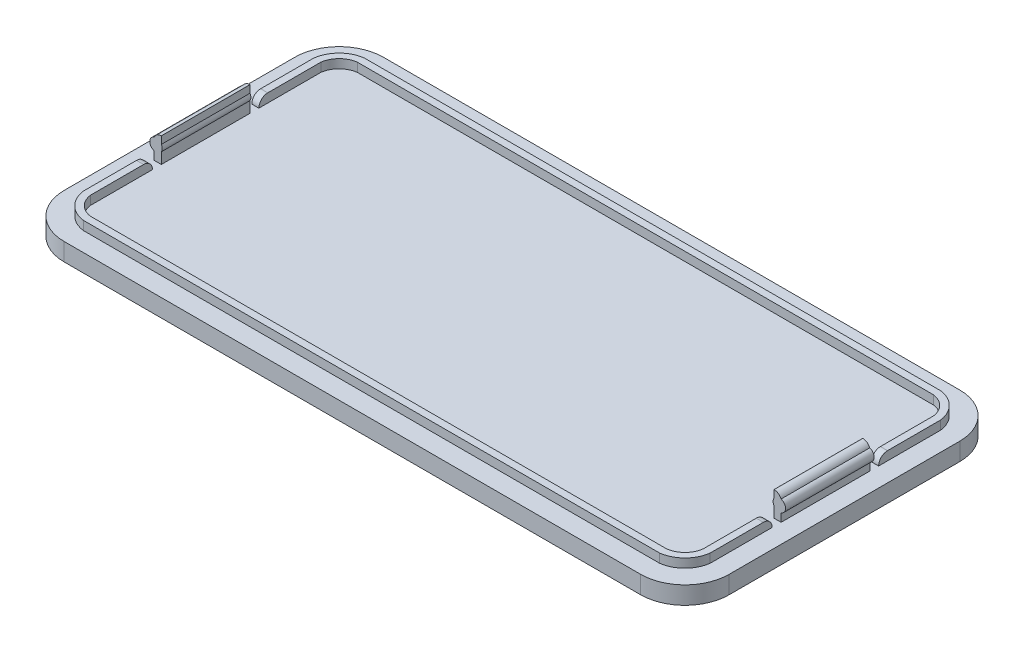
SolidWorks part; units mm, degrees
ref_plane "前视基准面" through (0, 0, 0) normal (0, 0, 1) x (1, 0, 0)
ref_plane "上视基准面" through (0, 0, 0) normal (0, 1, 0) x (1, 0, 0)
ref_plane "右视基准面" through (0, 0, 0) normal (1, 0, 0) x (0, 0, -1)
sketch "zero" plane through (0, 0, 0) normal (0, 1, 0) x (1, 0, 0)
  line L1 (-29.5, 15) -> (29.5, 15)
  line L2 (-32.5, 12) -> (-32.5, -12)
  line L3 (-29.5, -15) -> (29.5, -15)
  line L4 (32.5, 12) -> (32.5, -12)
  line L5 (-32.5, 15) -> (32.5, -15) construction
  line L6 (-32.5, -15) -> (32.5, 15) construction
  line L7 (-25.7, -15) -> (-14.5, -15)
  line L8 (-25.7, -15) -> (-25.7, -9.6569)
  line L9 (-25.7, -9.6569) -> (-14.5, -9.6569)
  line L10 (-14.5, -15) -> (-14.5, -9.6569)
  line L11 (5.2, -15) -> (12.7, -15)
  line L12 (5.2, -15) -> (5.2, -11)
  line L13 (5.2, -11) -> (12.7, -11)
  line L14 (12.7, -15) -> (12.7, -11)
  line L15 (17.8, -15) -> (25.3, -15)
  line L16 (17.8, -15) -> (17.8, -11)
  line L17 (17.8, -11) -> (25.3, -11)
  line L18 (25.3, -15) -> (25.3, -11)
  line L19 (-32.5, 7.7) -> (-19.5, 7.7)
  line L20 (-32.5, 7.7) -> (-32.5, -4.3)
  line L21 (-32.5, -4.3) -> (-19.5, -4.3)
  line L22 (-19.5, 7.7) -> (-19.5, -4.3)
  line L23 (-25.5, 14) -> (25.5, 14)
  line L24 (-25.5, 14) -> (-25.5, 8.8)
  line L25 (-25.5, 8.8) -> (25.5, 8.8)
  line L26 (25.5, 14) -> (25.5, 8.8)
  line L27 (-19.5, 7.2329) -> (-35.5, 7.2329)
  line L28 (-19.5, 7.2329) -> (-19.5, -3.7671)
  line L29 (-19.5, -3.7671) -> (-35.5, -3.7671)
  line L30 (-35.5, 7.2329) -> (-35.5, -3.7671)
  arc A0 (29.5, -15) -> (32.5, -12) centre (29.5, -12) ccw
  arc A1 (29.5, 15) -> (32.5, 12) centre (29.5, 12) cw
  arc A2 (-32.5, -12) -> (-29.5, -15) centre (-29.5, -12) ccw
  arc A3 (-29.5, 15) -> (-32.5, 12) centre (-29.5, 12) ccw
  circle A4 centre (-29, 11.4) radius 3
  circle A5 centre (-29, -11.5) radius 3
  circle A6 centre (29, 11.4) radius 3
  circle A7 centre (29, -11.5) radius 3
  circle A8 centre (-29, 11.4) radius 1.375
  circle A9 centre (-29, -11.5) radius 1.375
  circle A10 centre (29, -11.5) radius 1.375
  circle A11 centre (29, 11.4) radius 1.375
  point P0 (0, 0)
  dimension "D3" = 3
  dimension "D4" = 6
  dimension "D9" = 2.75
  dimension "D1" = 65
  dimension "D2" = 30
  dimension "D5" = 3.6
  dimension "D6" = 3.5
  dimension "D7" = 3.5
  dimension "D8" = 3.5
  dimension "D10" = 12
  dimension "D11" = 7.3
  dimension "D12" = 13
  dimension "D13" = 11.2
  dimension "D14" = 6.8
  dimension "D15" = 19.7
  dimension "D16" = 7.5
  dimension "D17" = 7.5
  dimension "D18" = 5.1
  dimension "D19" = 4
  dimension "D20" = 5.2
  dimension "D21" = 7
  dimension "D22" = 7
  dimension "D23" = 1
  dimension "D24" = 11
  dimension "D25" = 16
sketch "sugar" plane through (0, 0, 0) normal (0, 1, 0) x (1, 0, 0)
  line L1 (-29.5, 15) -> (29.5, 15)
  line L2 (-32.5, 12) -> (-32.5, -12)
  line L3 (-29.5, -15) -> (29.5, -15)
  line L4 (32.5, 12) -> (32.5, -12)
  line L5 (-32.5, 15) -> (32.5, -15) construction
  line L6 (-32.5, -15) -> (32.5, 15) construction
  line L7 (23.5, -11.5) -> (19.5, -11.5)
  line L8 (23.5, -11.5) -> (23.5, -13.9082)
  line L9 (23.5, -13.9082) -> (19.5, -13.9082)
  line L10 (19.5, -11.5) -> (19.5, -13.9082)
  line L11 (16, -11.0071) -> (8.5, -11.0071)
  line L12 (16, -11.0071) -> (16, -15)
  line L13 (16, -15) -> (8.5, -15)
  line L14 (8.5, -11.0071) -> (8.5, -15)
  line L15 (20.5, -13.9082) -> (22.5, -13.9082)
  line L16 (20.5, -13.9082) -> (20.5, -14.8173)
  line L17 (20.5, -14.8173) -> (22.5, -14.8173)
  line L18 (22.5, -13.9082) -> (22.5, -14.8173)
  arc A0 (29.5, 15) -> (32.5, 12) centre (29.5, 12) cw
  arc A1 (29.5, -15) -> (32.5, -12) centre (29.5, -12) ccw
  arc A2 (-32.5, -12) -> (-29.5, -15) centre (-29.5, -12) ccw
  arc A3 (-29.5, 15) -> (-32.5, 12) centre (-29.5, 12) ccw
  circle A4 centre (-29, 11.4) radius 3
  circle A5 centre (-29, 11.4) radius 1.375
  circle A6 centre (-29, -11.5) radius 3
  circle A7 centre (-29, -11.5) radius 1.375
  circle A8 centre (29, 11.4) radius 3
  circle A9 centre (29, 11.4) radius 1.375
  circle A10 centre (29, -11.5) radius 3
  circle A11 centre (29, -11.5) radius 1.375
  dimension "D3" = 3
  dimension "D1" = 65
  dimension "D2" = 30
  dimension "D4" = 9
  dimension "D5" = 4
  dimension "D6" = 3.5
  dimension "D7" = 7.5
  dimension "D8" = 2
  dimension "D9" = 1
sketch "case" plane through (0, 0, 0) normal (0, 1, 0) x (1, 0, 0)
  line L1 (-34.0422, 18) -> (30.9578, 18)
  line L2 (-39.0422, 13) -> (-39.0422, -13)
  line L3 (-34.0422, -18) -> (30.9578, -18)
  line L4 (35.9578, 13) -> (35.9578, -13)
  line L5 (-39.0422, 18) -> (35.9578, -18) construction
  line L6 (-39.0422, -18) -> (35.9578, 18) construction
  arc A0 (-39.0422, -13) -> (-34.0422, -18) centre (-34.0422, -13) ccw
  arc A1 (30.9578, -18) -> (35.9578, -13) centre (30.9578, -13) ccw
  arc A2 (30.9578, 18) -> (35.9578, 13) centre (30.9578, 13) cw
  arc A3 (-34.0422, 18) -> (-39.0422, 13) centre (-34.0422, 13) ccw
  point P0 (-1.5422, 0)
  point P3 (-1.5422, 0)
  dimension "D3" = 5
  dimension "D1" = 75
  dimension "D2" = 36
extrude "凸台-拉伸2" add sketch "case" along normal blind 2
sketch "草图2" plane through (0, 0, 0) normal (0, 1, 0) x (1, 0, 0)
  line L4 (-34.0422, -15.05) -> (30.9578, -15.05)
  line L5 (33.0078, -13) -> (33.0078, 13)
  line L6 (30.9578, 15.05) -> (-34.0422, 15.05)
  line L7 (-36.0922, 13) -> (-36.0922, -13)
  line L12 (33.8078, -13) -> (33.8078, 13)
  line L13 (30.9578, 15.85) -> (-34.0422, 15.85)
  line L14 (-36.8922, 13) -> (-36.8922, -13)
  line L15 (-34.0422, -15.85) -> (30.9578, -15.85)
  arc A4 (30.9578, -15.05) -> (33.0078, -13) centre (30.6303, -12.6725) ccw
  arc A5 (33.0078, 13) -> (30.9578, 15.05) centre (30.6303, 12.6725) ccw
  arc A6 (-34.0422, 15.05) -> (-36.0922, 13) centre (-33.7147, 12.6725) ccw
  arc A7 (-36.0922, -13) -> (-34.0422, -15.05) centre (-33.7147, -12.6725) ccw
  arc A12 (30.9578, -15.85) -> (33.8078, -13) centre (30.535, -12.5772) ccw
  arc A13 (33.8078, 13) -> (30.9578, 15.85) centre (30.535, 12.5772) ccw
  arc A14 (-34.0422, 15.85) -> (-36.8922, 13) centre (-33.6194, 12.5772) ccw
  arc A15 (-36.8922, -13) -> (-34.0422, -15.85) centre (-33.6194, -12.5772) ccw
  point P13 (0, 0)
  point P14 (0, 0)
ref_plane "基准面1" through (0, 2, 0) normal (0, 1, 0) x (1, 0, 0)
sketch "草图3" plane through (0, 2, 0) normal (0, 1, 0) x (1, 0, 0)
  line L4 (-34.0422, -15.05) -> (30.9578, -15.05)
  line L5 (33.0078, -13) -> (33.0078, 13)
  line L6 (30.9578, 15.05) -> (-34.0422, 15.05)
  line L7 (-36.0922, 13) -> (-36.0922, -13)
  line L8 (-34.0422, -15.05) -> (30.9578, -15.05)
  line L9 (33.0078, -13) -> (33.0078, 13)
  line L10 (30.9578, 15.05) -> (-34.0422, 15.05)
  line L11 (-36.0922, 13) -> (-36.0922, -13)
  line L12 (-36.8922, 13) -> (-36.8922, -13)
  line L13 (-34.0422, -15.85) -> (30.9578, -15.85)
  line L14 (33.8078, -13) -> (33.8078, 13)
  line L15 (30.9578, 15.85) -> (-34.0422, 15.85)
  line L16 (-36.8922, 13) -> (-36.8922, -13)
  line L17 (-34.0422, -15.85) -> (30.9578, -15.85)
  line L18 (33.8078, -13) -> (33.8078, 13)
  line L19 (30.9578, 15.85) -> (-34.0422, 15.85)
  arc A4 (30.9578, -15.05) -> (33.0078, -13) centre (30.6303, -12.6725) ccw
  arc A5 (33.0078, 13) -> (30.9578, 15.05) centre (30.6303, 12.6725) ccw
  arc A6 (-34.0422, 15.05) -> (-36.0922, 13) centre (-33.7147, 12.6725) ccw
  arc A7 (-36.0922, -13) -> (-34.0422, -15.05) centre (-33.7147, -12.6725) ccw
  arc A8 (30.9578, -15.05) -> (33.0078, -13) centre (30.6303, -12.6725) ccw
  arc A9 (33.0078, 13) -> (30.9578, 15.05) centre (30.6303, 12.6725) ccw
  arc A10 (-34.0422, 15.05) -> (-36.0922, 13) centre (-33.7147, 12.6725) ccw
  arc A11 (-36.0922, -13) -> (-34.0422, -15.05) centre (-33.7147, -12.6725) ccw
  arc A12 (-36.8922, -13) -> (-34.0422, -15.85) centre (-33.6194, -12.5772) ccw
  arc A13 (30.9578, -15.85) -> (33.8078, -13) centre (30.535, -12.5772) ccw
  arc A14 (33.8078, 13) -> (30.9578, 15.85) centre (30.535, 12.5772) ccw
  arc A15 (-34.0422, 15.85) -> (-36.8922, 13) centre (-33.6194, 12.5772) ccw
  arc A16 (-36.8922, -13) -> (-34.0422, -15.85) centre (-33.6194, -12.5772) ccw
  arc A17 (30.9578, -15.85) -> (33.8078, -13) centre (30.535, -12.5772) ccw
  arc A18 (33.8078, 13) -> (30.9578, 15.85) centre (30.535, 12.5772) ccw
  arc A19 (-34.0422, 15.85) -> (-36.8922, 13) centre (-33.6194, 12.5772) ccw
  dimension "D1" = 0
  dimension "D2" = 0
extrude "凸台-拉伸4" add sketch "草图3" along normal blind 1
ref_plane "基准面3" through (33.8078, 0, 0) normal (1, 0, 0) x (0, 0, -1)
sketch "草图7" plane through (0, 2, 0) normal (0, 1, 0) x (1, 0, 0)
  line L0 (-36.8922, 13) -> (-36.8922, -13) construction
  line L1 (-36.8922, 5) -> (-36.0922, 5)
  line L2 (-36.8922, 5) -> (-36.8922, -5)
  line L3 (-36.8922, -5) -> (-36.0922, -5)
  line L4 (-36.0922, 5) -> (-36.0922, -5)
  line L5 (-36.0922, 13) -> (-36.0922, -13) construction
  point P10 (-36.0922, 0)
  dimension "D1" = 5
  dimension "D2" = 10
extrude "凸台-拉伸8" add sketch "草图7" along normal blind 2.8
ref_plane "基准面5" through (0, 0, 5) normal (0, 0, 1) x (1, 0, 0)
sketch "草图8" plane through (0, 0, 5) normal (0, 0, 1) x (1, 0, 0)
  line L0 (-34.0422, 2) -> (-39.0422, 2) construction
  line L1 (-36.8922, 4.8) -> (-36.8922, 3) construction
  circle A0 centre (-36.6922, 3.6) radius 0.7
  dimension "D1" = 1.4
  dimension "D2" = 1.6
  dimension "D3" = 0.2
extrude "凸台-拉伸9" add sketch "草图8" against normal blind 10
fillet "圆角1" radius 0.85 1 edges at (-36.8922, 4.8, 0)
ref_plane "基准面7" through (-36.8922, 0, 0) normal (-1, 0, 0) x (0, 0, 1)
sketch "草图11" plane through (-36.8922, 0, 0) normal (-1, 0, 0) x (0, 0, 1)
  line L0 (-13, 2) -> (13, 2) construction
  line L1 (5, 3) -> (6, 3)
  line L2 (5, 3) -> (5, 2)
  line L3 (5, 2) -> (6, 2)
  line L4 (6, 3) -> (6, 2)
  line L6 (-5, 3) -> (-6, 3)
  line L7 (-5, 3) -> (-5, 2)
  line L8 (-5, 2) -> (-6, 2)
  line L9 (-6, 3) -> (-6, 2)
  dimension "D1" = 1
  dimension "D2" = 1
extrude "切除-拉伸1" cut sketch "草图11" against normal blind 1.2
fillet "圆角2" radius 1 2 edges at (-36.4922, 3, 6) (-36.4922, 3, -6)
ref_plane "基准面8" through (0, 0, 0) normal (0, -1, 0) x (-1, 0, 0)
sketch "草图12" plane through (0, 0, 0) normal (0, -1, 0) x (-1, 0, 0)
  line L76 (34.0422, -18) -> (-30.9578, -18) construction
  line L78 (39.0422, 13) -> (39.0422, -13) construction
  line B0 (-8.1993, 5.026) -> (-9.0198, 5.499)
  line B1 (-9.0198, 5.499) -> (-13.2767, 7.9551)
  line B2 (-13.2767, 7.9551) -> (-14.0973, 8.4339)
  line B3 (-15.8183, 8.4339) -> (-16.6389, 7.9551)
  line B4 (-16.6389, 7.9551) -> (-20.8958, 5.499)
  line B5 (-20.8958, 5.499) -> (-21.7165, 5.026)
  line B6 (-22.577, 3.5387) -> (-22.577, -3.2769)
  line B7 (-21.7165, -4.7643) -> (-20.8958, -5.2373)
  line B8 (-20.8958, -5.2373) -> (-16.6389, -7.6934)
  line B9 (-16.6389, -7.6934) -> (-15.8183, -8.172)
  line B10 (-14.0973, -8.172) -> (-13.2767, -7.6934)
  line B11 (-13.2767, -7.6934) -> (-9.0198, -5.2373)
  line B12 (-9.0198, -5.2373) -> (-8.1993, -4.7643)
  line B13 (-7.3388, -3.2769) -> (-7.3388, 3.5387)
  line B14 (-20.6223, 4.3479) -> (-15.3568, 7.391)
  line B15 (-14.5532, 7.391) -> (-9.3162, 4.3422)
  line B16 (-9.3105, 3.6413) -> (-14.3993, 0.5982)
  line B17 (-12.8208, -4.5591) -> (-13.4135, -4.8896)
  line B18 (-13.4705, -4.9865) -> (-13.4705, -6.6961)
  line B19 (-13.5274, -6.793) -> (-14.633, -7.4198)
  line B20 (-14.7983, -7.3229) -> (-14.7983, -2.046)
  line B21 (-14.7413, -1.9491) -> (-12.8607, -0.8835)
  line B22 (-8.9173, -4.2058) -> (-10.0114, -4.8269)
  line B23 (-10.1767, -4.7301) -> (-10.1767, -2.2169)
  line B24 (-10.1197, -2.1201) -> (-9.0256, -1.5046)
  line B25 (-8.8603, -1.6015) -> (-8.8603, -4.1089)
  line B26 (-12.8893, -3.5447) -> (-13.4135, -3.8069)
  line B27 (-13.4705, -3.6872) -> (-13.4705, -2.3423)
  line B28 (-13.4135, -2.2455) -> (-12.9234, -1.9719)
  line B29 (-3.344, 3.06) -> (-5.2189, 3.06)
  line B30 (-5.2189, 3.06) -> (-5.2189, -3.5048)
  line B31 (-5.2189, -3.5048) -> (-4.3868, -3.5048)
  line B32 (-4.3868, -3.5048) -> (-4.3868, -0.9005)
  line B33 (-4.3868, -0.9005) -> (-3.2984, -0.9005)
  line B34 (-3.4066, -0.2281) -> (-4.3868, -0.2281)
  line B35 (-4.3868, -0.2281) -> (-4.3868, 2.3876)
  line B36 (-4.3868, 2.3876) -> (-3.4408, 2.3876)
  line B37 (0.1948, 1.3618) -> (0.1948, -3.5048)
  line B38 (0.1948, -3.5048) -> (1.0098, -3.5048)
  line B39 (1.0098, -3.5048) -> (1.0098, 1.3618)
  line B40 (1.0098, 1.3618) -> (0.1948, 1.3618)
  line B41 (5.7169, 0.2847) -> (4.8849, 0.6153)
  line B42 (6.0417, 1.4017) -> (6.8396, 2.4047)
  line B43 (3.6084, -0.5586) -> (4.4575, -0.9177)
  line B44 (2.9074, -1.5673) -> (2.0014, -2.6729)
  line B45 (10.8229, 1.5898) -> (10.8229, -1.7497)
  line B46 (9.3811, -1.3621) -> (9.3811, 1.5898)
  line B47 (9.3811, 1.5898) -> (7.7912, 1.5898)
  line B48 (7.7912, 1.5898) -> (7.7912, -1.5616)
  line B49 (10.9711, -2.8039) -> (11.0052, -2.8039)
  line B50 (11.0052, -2.8039) -> (11.1193, -3.5048)
  line B51 (11.1193, -3.5048) -> (12.4185, -3.5048)
  line B52 (12.4185, -3.5048) -> (12.4185, 1.5898)
  line B53 (12.4185, 1.5898) -> (10.8229, 1.5898)
  line B54 (16.2708, -2.5019) -> (15.4673, -2.5019)
  line B55 (17.365, 0.4386) -> (18.1513, 0.4386)
  line B56 (18.1513, 0.4386) -> (18.1513, 1.5898)
  line B57 (18.1513, 1.5898) -> (16.2822, 1.5898)
  line B58 (14.0312, -1.4533) -> (14.0312, -1.4875)
  line B59 (13.9344, -3.3168) -> (13.9344, -3.3624)
  line B60 (15.4844, -3.7214) -> (15.9688, -3.7214)
  line B61 (18.6072, 1.0484) -> (19.1657, -0.0002)
  line B62 (21.411, -2.992) -> (21.4508, -2.992)
  line B63 (21.4508, -2.992) -> (21.5648, -3.5048)
  line B64 (21.5648, -3.5048) -> (22.8641, -3.5048)
  line B65 (22.8641, -3.5048) -> (22.8641, -0.6099)
  line B66 (21.2685, -1.1741) -> (21.2685, -1.989)
  line B67 (25.3545, 0.7065) -> (25.3203, 0.7065)
  line B68 (25.3203, 0.7065) -> (25.212, 1.5898)
  line B69 (25.212, 1.5898) -> (23.9127, 1.5898)
  line B70 (23.9127, 1.5898) -> (23.9127, -3.5048)
  line B71 (23.9127, -3.5048) -> (25.4969, -3.5048)
  line B72 (25.4969, -3.5048) -> (25.4969, -0.5928)
  line B73 (27.1552, 0.2392) -> (27.423, 1.6125)
  line B74 (-13.4135, -3.8069) -> (-13.4135, -4.8896)
  line B75 (-13.4705, -3.6872) -> (-13.4705, -4.9865)
  spline B76 degree 3 poles (-14.0973, 8.4339) (-14.3652, 8.582) (-14.6615, 8.6618) (-14.9578, 8.6618) knots 3 3 3 3 4 4 4 4
  spline B77 degree 3 poles (-14.9578, 8.6618) (-15.2541, 8.6618) (-15.5505, 8.582) (-15.8183, 8.4339) knots 4 4 4 4 5 5 5 5
  spline B78 degree 3 poles (-21.7165, 5.026) (-22.2464, 4.7183) (-22.577, 4.1485) (-22.577, 3.5387) knots 8 8 8 8 9 9 9 9
  spline B79 degree 3 poles (-22.577, -3.2769) (-22.577, -3.8923) (-22.2464, -4.4565) (-21.7165, -4.7643) knots 10 10 10 10 11 11 11 11
  spline B80 degree 3 poles (-15.8183, -8.172) (-15.5505, -8.3259) (-15.2541, -8.4) (-14.9578, -8.4) knots 14 14 14 14 15 15 15 15
  spline B81 degree 3 poles (-14.9578, -8.4) (-14.6615, -8.4) (-14.3652, -8.3259) (-14.0973, -8.172) knots 15 15 15 15 16 16 16 16
  spline B82 degree 3 poles (-8.1993, -4.7643) (-7.6636, -4.4565) (-7.3388, -3.8923) (-7.3388, -3.2769) knots 19 19 19 19 20 20 20 20
  spline B83 degree 3 poles (-7.3388, 3.5387) (-7.3388, 4.1485) (-7.6636, 4.7183) (-8.1993, 5.026) knots 21 21 21 21 22 22 22 22
  spline B84 degree 2 poles (-15.5106, 0.5982) (-20.6622, 3.5729) (-20.6736, 3.5786) knots 0 0 0 1 1 1
  spline B85 degree 3 poles (-20.6736, 3.5786) (-20.9414, 3.7723) (-20.9129, 4.1826) (-20.6223, 4.3479) knots 1 1 1 1 2 2 2 2
  spline B86 degree 3 poles (-15.3568, 7.391) (-15.1117, 7.5335) (-14.8039, 7.5335) (-14.5532, 7.391) knots 3 3 3 3 4 4 4 4
  spline B87 degree 3 poles (-9.3162, 4.3422) (-9.0484, 4.1883) (-9.0427, 3.8008) (-9.3105, 3.6413) knots 5 5 5 5 6 6 6 6
  spline B88 degree 3 poles (-14.3993, 0.5982) (-14.7413, 0.3987) (-15.1687, 0.3987) (-15.5106, 0.5982) knots 7 7 7 7 8 8 8 8
  spline B89 degree 3 poles (-13.4705, -6.6961) (-13.4705, -6.736) (-13.4876, -6.7702) (-13.5274, -6.793) knots 3 3 3 3 4 4 4 4
  spline B90 degree 3 poles (-14.633, -7.4198) (-14.7071, -7.4597) (-14.7983, -7.4084) (-14.7983, -7.3229) knots 5 5 5 5 6 6 6 6
  spline B91 degree 3 poles (-14.7983, -2.046) (-14.7983, -2.0061) (-14.7812, -1.9662) (-14.7413, -1.9491) knots 7 7 7 7 8 8 8 8
  spline B92 degree 3 poles (-12.8607, -0.8835) (-11.6412, -0.1939) (-10.6326, -0.0572) (-10.6326, -1.4249) knots 9 9 9 9 10 10 10 10
  spline B93 degree 3 poles (-10.6326, -1.4249) (-10.6326, -2.7412) (-11.6526, -3.898) (-12.8208, -4.5591) knots 10 10 10 10 11 11 11 11
  spline B94 degree 3 poles (-8.8603, -4.1089) (-8.8603, -4.1488) (-8.8831, -4.1887) (-8.9173, -4.2058) knots 0 0 0 0 1 1 1 1
  spline B95 degree 3 poles (-10.0114, -4.8269) (-10.0855, -4.8668) (-10.1767, -4.8155) (-10.1767, -4.7301) knots 2 2 2 2 3 3 3 3
  spline B96 degree 3 poles (-10.1767, -2.2169) (-10.1767, -2.1771) (-10.1539, -2.1429) (-10.1197, -2.1201) knots 4 4 4 4 5 5 5 5
  spline B97 degree 3 poles (-9.0256, -1.5046) (-8.9515, -1.4647) (-8.8603, -1.516) (-8.8603, -1.6015) knots 6 6 6 6 7 7 7 7
  spline B98 degree 3 poles (-9.5156, 0.1651) (-9.0768, 0.4158) (-8.7634, 0.3076) (-8.7634, -0.0914) (-8.7634, -0.4846) (-9.0768, -0.9461) (-9.5156, -1.1912) knots 2 2 2 2 3 3 3 4 4 4 4
  spline B99 degree 3 poles (-9.5156, -1.1912) (-9.9601, -1.4476) (-10.2735, -1.3394) (-10.2735, -0.9461) (-10.2735, -0.5415) (-9.9601, -0.0856) (-9.5156, 0.1651) knots 0 0 0 0 1 1 1 2 2 2 2
  spline B100 degree 3 poles (-11.9319, -2.16) (-11.9319, -2.7013) (-12.2395, -3.18) (-12.8893, -3.5447) knots 0 0 0 0 1 1 1 1
  spline B101 degree 3 poles (-13.4705, -2.3423) (-13.4705, -2.3024) (-13.4477, -2.2625) (-13.4135, -2.2455) knots 4 4 4 4 5 5 5 5
  spline B102 degree 3 poles (-12.9234, -1.9719) (-12.2852, -1.6072) (-11.9319, -1.6015) (-11.9319, -2.16) knots 6 6 6 6 7 7 7 7
  spline B103 degree 3 poles (-3.2984, -0.9005) (-1.868, -0.9005) (-0.8822, -0.2509) (-0.8822, 1.1339) knots 5 5 5 5 6 6 6 6
  spline B104 degree 3 poles (-0.8822, 1.1339) (-0.8822, 2.5699) (-1.868, 3.06) (-3.344, 3.06) knots 6 6 6 6 7 7 7 7
  spline B105 degree 3 poles (-3.4408, 2.3876) (-2.2897, 2.3876) (-1.7084, 2.0855) (-1.7084, 1.1339) knots 3 3 3 3 4 4 4 4
  spline B106 degree 3 poles (-1.7084, 1.1339) (-1.7084, 0.1936) (-2.2498, -0.2281) (-3.4066, -0.2281) knots 4 4 4 4 5 5 5 5
  spline B107 degree 3 poles (0.6052, 2.3648) (0.93, 2.3648) (1.1694, 2.587) (1.1694, 2.889) (1.1694, 3.2253) (0.93, 3.419) (0.6052, 3.419) knots 2 2 2 2 3 3 3 4 4 4 4
  spline B108 degree 3 poles (0.6052, 3.419) (0.2804, 3.419) (0.041, 3.2253) (0.041, 2.889) (0.041, 2.587) (0.2804, 2.3648) (0.6052, 2.3648) knots 0 0 0 0 1 1 1 2 2 2 2
  spline B109 degree 3 poles (4.8849, 0.6153) (4.2979, 0.8489) (3.8762, 0.9914) (3.8762, 1.3618) knots 1 1 1 1 2 2 2 2
  spline B110 degree 3 poles (3.8762, 1.3618) (3.8762, 1.7151) (4.1783, 1.9146) (4.674, 1.9146) knots 2 2 2 2 3 3 3 3
  spline B111 degree 3 poles (4.674, 1.9146) (5.1926, 1.9146) (5.6029, 1.7379) (6.0417, 1.4017) knots 3 3 3 3 4 4 4 4
  spline B112 degree 3 poles (6.8396, 2.4047) (6.2583, 2.9916) (5.4433, 3.2879) (4.674, 3.2879) knots 5 5 5 5 6 6 6 6
  spline B113 degree 3 poles (4.674, 3.2879) (3.2551, 3.2879) (2.2521, 2.3876) (2.2521, 1.2706) knots 6 6 6 6 7 7 7 7
  spline B114 degree 3 poles (2.2521, 1.2706) (2.2521, 0.3019) (2.9074, -0.2794) (3.6084, -0.5586) knots 7 7 7 7 8 8 8 8
  spline B115 degree 3 poles (4.4575, -0.9177) (5.0274, -1.157) (5.3978, -1.2824) (5.3978, -1.6699) knots 9 9 9 9 10 10 10 10
  spline B116 degree 3 poles (5.3978, -1.6699) (5.3978, -2.0289) (5.1185, -2.2511) (4.5259, -2.2511) knots 10 10 10 10 11 11 11 11
  spline B117 degree 3 poles (4.5259, -2.2511) (4.0016, -2.2511) (3.3804, -1.9719) (2.9074, -1.5673) knots 11 11 11 11 12 12 12 12
  spline B118 degree 3 poles (2.0014, -2.6729) (2.6909, -3.3054) (3.6254, -3.6302) (4.4916, -3.6302) knots 13 13 13 13 14 14 14 14
  spline B119 degree 3 poles (4.4916, -3.6302) (6.1044, -3.6302) (7.0389, -2.6557) (7.0389, -1.5445) knots 14 14 14 14 15 15 15 15
  spline B120 degree 3 poles (7.0389, -1.5445) (7.0389, -0.6042) (6.5432, -0.0458) (5.7169, 0.2847) knots 15 15 15 15 16 16 16 16
  spline B121 degree 3 poles (10.8229, -1.7497) (10.5551, -2.1258) (10.3328, -2.2682) (9.9738, -2.2682) knots 1 1 1 1 2 2 2 2
  spline B122 degree 3 poles (9.9738, -2.2682) (9.5692, -2.2682) (9.3811, -2.0688) (9.3811, -1.3621) knots 2 2 2 2 3 3 3 3
  spline B123 degree 3 poles (7.7912, -1.5616) (7.7912, -2.8324) (8.2642, -3.6302) (9.3754, -3.6302) knots 6 6 6 6 7 7 7 7
  spline B124 degree 3 poles (9.3754, -3.6302) (10.0706, -3.6302) (10.5494, -3.3054) (10.9711, -2.8039) knots 7 7 7 7 8 8 8 8
  spline B125 degree 3 poles (15.4673, -2.5019) (14.9202, -2.5019) (14.7151, -2.3936) (14.7151, -2.16) knots 1 1 1 1 2 2 2 2
  spline B126 degree 3 poles (14.7151, -2.16) (14.7151, -1.989) (14.7549, -1.9092) (14.8746, -1.8009) knots 2 2 2 2 3 3 3 3
  spline B127 degree 3 poles (14.8746, -1.8009) (15.0969, -1.8636) (15.302, -1.8921) (15.473, -1.8921) knots 3 3 3 3 4 4 4 4
  spline B128 degree 3 poles (15.473, -1.8921) (16.6013, -1.8921) (17.5074, -1.3735) (17.5074, -0.1825) knots 4 4 4 4 5 5 5 5
  spline B129 degree 3 poles (17.5074, -0.1825) (17.5074, 0.0625) (17.4447, 0.2962) (17.365, 0.4386) knots 5 5 5 5 6 6 6 6
  spline B130 degree 3 poles (16.2822, 1.5898) (16.0485, 1.6752) (15.7693, 1.7151) (15.473, 1.7151) knots 9 9 9 9 10 10 10 10
  spline B131 degree 3 poles (15.473, 1.7151) (14.3732, 1.7151) (13.3417, 1.1111) (13.3417, -0.1369) knots 10 10 10 10 11 11 11 11
  spline B132 degree 3 poles (13.3417, -0.1369) (13.3417, -0.7296) (13.6722, -1.2026) (14.0312, -1.4533) knots 11 11 11 11 12 12 12 12
  spline B133 degree 3 poles (14.0312, -1.4875) (13.7007, -1.7212) (13.467, -2.0802) (13.467, -2.4392) knots 13 13 13 13 14 14 14 14
  spline B134 degree 3 poles (13.467, -2.4392) (13.467, -2.8666) (13.6665, -3.1344) (13.9344, -3.3168) knots 14 14 14 14 15 15 15 15
  spline B135 degree 3 poles (13.9344, -3.3624) (13.4613, -3.6017) (13.2106, -3.9436) (13.2106, -4.3653) knots 16 16 16 16 17 17 17 17
  spline B136 degree 3 poles (13.2106, -4.3653) (13.2106, -5.2771) (14.1737, -5.6475) (15.3476, -5.6475) knots 17 17 17 17 18 18 18 18
  spline B137 degree 3 poles (15.3476, -5.6475) (17.1199, -5.6475) (18.2312, -4.8839) (18.2312, -3.8069) knots 18 18 18 18 19 19 19 19
  spline B138 degree 3 poles (18.2312, -3.8069) (18.2312, -2.8837) (17.5245, -2.5019) (16.2708, -2.5019) knots 19 19 19 19 20 20 20 20
  spline B139 degree 3 poles (15.473, -0.9347) (15.1083, -0.9347) (14.8291, -0.6669) (14.8291, -0.1369) (14.8291, 0.3816) (15.1083, 0.6495) (15.473, 0.6495) knots 2 2 2 2 3 3 3 4 4 4 4
  spline B140 degree 3 poles (15.473, 0.6495) (15.8491, 0.6495) (16.1169, 0.3816) (16.1169, -0.1369) (16.1169, -0.6669) (15.8491, -0.9347) (15.473, -0.9347) knots 0 0 0 0 1 1 1 2 2 2 2
  spline B141 degree 3 poles (15.5983, -4.6503) (14.943, -4.6503) (14.5156, -4.4736) (14.5156, -4.1146) knots 0 0 0 0 1 1 1 1
  spline B142 degree 3 poles (14.5156, -4.1146) (14.5156, -3.9436) (14.5953, -3.8012) (14.7549, -3.6587) knots 1 1 1 1 2 2 2 2
  spline B143 degree 3 poles (14.7549, -3.6587) (14.9202, -3.7043) (15.114, -3.7214) (15.4844, -3.7214) knots 2 2 2 2 3 3 3 3
  spline B144 degree 3 poles (15.9688, -3.7214) (16.4417, -3.7214) (16.7096, -3.7841) (16.7096, -4.0861) knots 4 4 4 4 5 5 5 5
  spline B145 degree 3 poles (16.7096, -4.0861) (16.7096, -4.4109) (16.2537, -4.6503) (15.5983, -4.6503) knots 5 5 5 5 6 6 6 6
  spline B146 degree 3 poles (20.8013, 1.7151) (20.0091, 1.7151) (19.2797, 1.4473) (18.6072, 1.0484) knots 0 0 0 0 1 1 1 1
  spline B147 degree 3 poles (19.1657, -0.0002) (19.6729, 0.2847) (20.0946, 0.4443) (20.4992, 0.4443) knots 2 2 2 2 3 3 3 3
  spline B148 degree 3 poles (20.4992, 0.4443) (21.0177, 0.4443) (21.2344, 0.205) (21.2685, -0.2053) knots 3 3 3 3 4 4 4 4
  spline B149 degree 3 poles (21.2685, -0.2053) (19.2797, -0.4219) (18.4362, -1.0031) (18.4362, -2.0802) knots 4 4 4 4 5 5 5 5
  spline B150 degree 3 poles (18.4362, -2.0802) (18.4362, -2.9293) (19.0118, -3.6302) (19.9522, -3.6302) knots 5 5 5 5 6 6 6 6
  spline B151 degree 3 poles (19.9522, -3.6302) (20.5163, -3.6302) (20.9893, -3.3681) (21.411, -2.992) knots 6 6 6 6 7 7 7 7
  spline B152 degree 3 poles (22.8641, -0.6099) (22.8641, 0.9857) (22.1176, 1.7151) (20.8013, 1.7151) knots 11 11 11 11 12 12 12 12
  spline B153 degree 3 poles (21.2685, -1.989) (21.0349, -2.2398) (20.824, -2.3936) (20.4992, -2.3936) knots 0 0 0 0 1 1 1 1
  spline B154 degree 3 poles (20.4992, -2.3936) (20.1686, -2.3936) (19.9522, -2.2511) (19.9522, -1.9548) knots 1 1 1 1 2 2 2 2
  spline B155 degree 3 poles (19.9522, -1.9548) (19.9522, -1.5958) (20.277, -1.3109) (21.2685, -1.1741) knots 2 2 2 2 3 3 3 3
  spline B156 degree 3 poles (26.8076, 1.7151) (26.2947, 1.7151) (25.7305, 1.3846) (25.3545, 0.7065) knots 0 0 0 0 1 1 1 1
  spline B157 degree 3 poles (25.4969, -0.5928) (25.7648, 0.0796) (26.2207, 0.3189) (26.5967, 0.3189) knots 7 7 7 7 8 8 8 8
  spline B158 degree 3 poles (26.5967, 0.3189) (26.8247, 0.3189) (26.9729, 0.2847) (27.1552, 0.2392) knots 8 8 8 8 9 9 9 9
  spline B159 degree 3 poles (27.423, 1.6125) (27.2806, 1.6752) (27.1096, 1.7151) (26.8076, 1.7151) knots 10 10 10 10 11 11 11 11
  dimension "D1" = 9.6
  dimension "D2" = 54
sketch_block_instance "块1-1"
sketch_block "块1"
extrude "切除-拉伸2" cut sketch "草图12" against normal blind 0.5
sketch "草图13" plane through (0, 3, 0) normal (0, 1, 0) x (1, 0, 0)
  line L0 (33.0078, -13) -> (33.0078, 13) construction
  line L1 (33.0078, 5) -> (33.8078, 5)
  line L2 (33.0078, 5) -> (33.0078, -5)
  line L3 (33.0078, -5) -> (33.8078, -5)
  line L4 (33.8078, 5) -> (33.8078, -5)
  line L5 (33.8078, -13) -> (33.8078, 13) construction
  line L7 (35.9578, -13) -> (35.9578, 13) construction
  point P12 (35.9578, 0)
  point P13 (33.8078, 0)
  dimension "D1" = 10
extrude "凸台-拉伸10" add sketch "草图13" along normal blind 1.8
sketch "草图14" plane through (0, 0, 5) normal (0, 0, 1) x (1, 0, 0)
  line L0 (33.8078, 2) -> (30.9578, 2) construction
  line L1 (33.8078, 4.8) -> (33.8078, 3) construction
  circle A0 centre (33.6078, 3.6) radius 0.7
  dimension "D2" = 1.4
  dimension "D1" = 1.6
  dimension "D3" = 0.2
extrude "凸台-拉伸11" add sketch "草图14" against normal blind 10
fillet "圆角3" radius 0.85 1 edges at (33.8078, 4.8, 0)
sketch "草图15" plane through (0, 3, 0) normal (0, 1, 0) x (1, 0, 0)
  line L0 (33.8078, 5) -> (33.8078, 13) construction
  line L1 (33.0078, 5) -> (33.8078, 5)
  line L2 (33.0078, 5) -> (33.0078, 6)
  line L3 (33.0078, 6) -> (33.8078, 6)
  line L4 (33.8078, 5) -> (33.8078, 6)
  line L5 (33.8078, -13) -> (33.8078, -5) construction
  line L6 (33.0078, -5) -> (33.8078, -5)
  line L7 (33.0078, -5) -> (33.0078, -6)
  line L8 (33.0078, -6) -> (33.8078, -6)
  line L9 (33.8078, -5) -> (33.8078, -6)
  dimension "D1" = 1
  dimension "D2" = 1
extrude "切除-拉伸3" cut sketch "草图15" against normal blind 1
fillet "圆角4" radius 1 2 edges at (33.4078, 3, 6) (33.4078, 3, -6)
